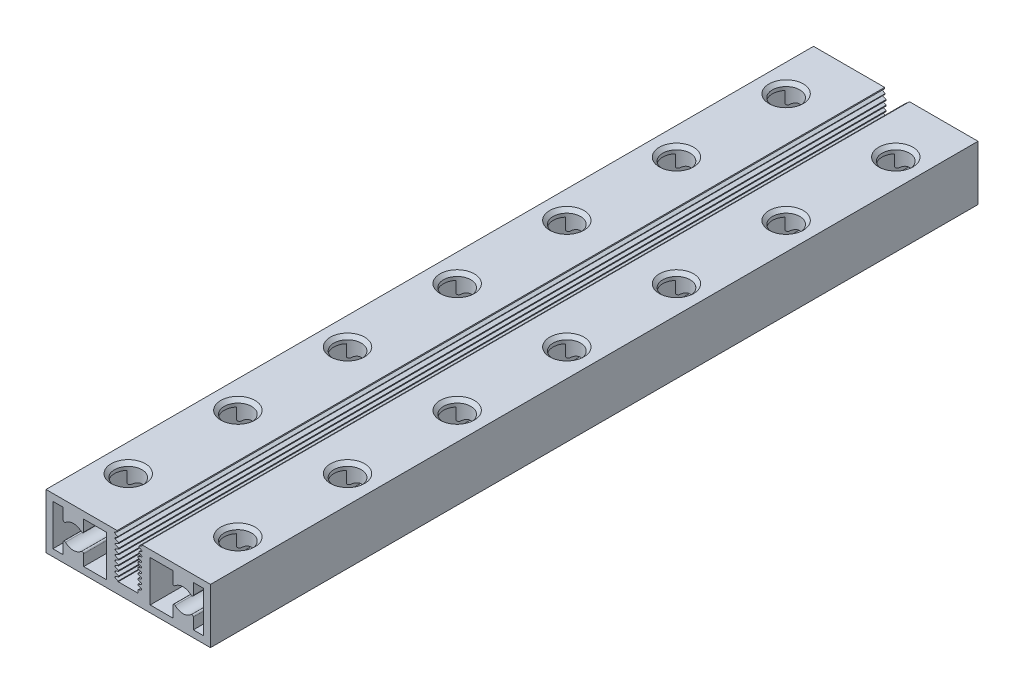
SolidWorks part; units mm, degrees
ref_plane "Front Plane" through (0, 0, 0) normal (0, 0, 1) x (1, 0, 0)
ref_plane "Top Plane" through (0, 0, 0) normal (0, 1, 0) x (1, 0, 0)
ref_plane "Right Plane" through (0, 0, 0) normal (1, 0, 0) x (0, 0, -1)
ref_plane "Plane1" through (0, 8, 0) normal (0, 1, 0) x (1, 0, 0)
sketch "Sketch1" plane through (0, 8, 0) normal (0, 1, 0) x (1, 0, 0)
  line L0 (-12, -112) -> (12, -112)
  line L1 (12, -112) -> (12, 0)
  line L2 (12, 0) -> (-12, 0)
  line L3 (-12, 0) -> (-12, -112)
extrude "Boss-Extrude1" add sketch "Sketch1" against normal blind 8
sketch "Sketch2" plane through (0, 0, 112) normal (0, 0, 1) x (1, 0, 0)
  line L0 (2, 8) -> (-1.62, 8)
  line L1 (-1.62, 8) -> (-1.62, 7.825)
  line L2 (-1.62, 7.825) -> (-2.0747, 7.5625)
  line L3 (-2.0747, 7.5625) -> (-1.4684, 7.2125)
  line L4 (-1.4684, 7.2125) -> (-2.0878, 6.8549)
  line L5 (-2.0878, 6.8549) -> (-1.2404, 6.5125)
  line L6 (-1.2404, 6.5125) -> (-2.1067, 6.1625)
  line L7 (-2.1067, 6.1625) -> (-1.2404, 5.8125)
  line L8 (-1.2404, 5.8125) -> (-2.1067, 5.4625)
  line L9 (-2.1067, 5.4625) -> (-1.2404, 5.1125)
  line L10 (-1.2404, 5.1125) -> (-2.1067, 4.7625)
  line L11 (-2.1067, 4.7625) -> (-1.2404, 4.4125)
  line L12 (-1.2404, 4.4125) -> (-2.1067, 4.0625)
  line L13 (-2.1067, 4.0625) -> (-1.2404, 3.7125)
  line L14 (-1.2404, 3.7125) -> (-2.1067, 3.3625)
  line L15 (-2.1067, 3.3625) -> (-1.2404, 3.0125)
  line L16 (-1.2404, 3.0125) -> (-2.1067, 2.6625)
  line L17 (-2.1067, 2.6625) -> (-1.2404, 2.3125)
  line L18 (-1.2404, 2.3125) -> (-2.1067, 1.9625)
  line L19 (-2.1067, 1.9625) -> (-1.46, 1.7012)
  line L20 (-1.46, 1.7012) -> (-1.46, 1.6)
  line L21 (-1.46, 1.6) -> (1.46, 1.6)
  line L22 (1.46, 1.6) -> (1.46, 2.0618)
  line L23 (1.46, 2.0618) -> (2.1067, 2.3231)
  line L24 (2.1067, 2.3231) -> (1.2404, 2.6731)
  line L25 (1.2404, 2.6731) -> (2.1067, 3.0231)
  line L26 (2.1067, 3.0231) -> (1.2404, 3.3731)
  line L27 (1.2404, 3.3731) -> (2.1067, 3.7231)
  line L28 (2.1067, 3.7231) -> (1.2404, 4.0731)
  line L29 (1.2404, 4.0731) -> (2.1067, 4.4231)
  line L30 (2.1067, 4.4231) -> (1.2404, 4.7731)
  line L31 (1.2404, 4.7731) -> (2.1067, 5.1231)
  line L32 (2.1067, 5.1231) -> (1.2404, 5.4731)
  line L33 (1.2404, 5.4731) -> (2.1067, 5.8231)
  line L34 (2.1067, 5.8231) -> (1.2404, 6.1731)
  line L35 (1.2404, 6.1731) -> (2.0878, 6.5155)
  line L36 (2.0878, 6.5155) -> (1.4684, 6.8731)
  line L37 (1.4684, 6.8731) -> (2.0747, 7.2231)
  line L38 (2.0747, 7.2231) -> (1.4684, 7.5731)
  line L39 (1.4684, 7.5731) -> (2, 7.88)
  line L40 (2, 7.88) -> (2, 8)
extrude "Cut-Extrude1" cut sketch "Sketch2" against normal through all
sketch "Sketch3" plane through (0, 0, 0) normal (0, 0, -1) x (-1, 0, 0)
  line L0 (-6.5, 2.6144) -> (-6.5, 1)
  line L1 (-6.5, 1) -> (-3.2, 1)
  line L2 (-3.2, 1) -> (-3.2, 7)
  line L3 (-3.2, 7) -> (-6.5, 7)
  line L4 (-6.5, 7) -> (-6.5, 5.3856)
  line L5 (-9.5, 5.3856) -> (-9.5, 7)
  line L6 (-9.5, 7) -> (-11, 7)
  line L7 (-11, 7) -> (-11, 1)
  line L8 (-11, 1) -> (-9.5, 1)
  line L9 (-9.5, 1) -> (-9.5, 2.6144)
  arc A0 (-6.5, 5.3856) -> (-6.8368, 5.2398) centre (-6.7, 5.3856) cw
  arc A1 (-6.8368, 5.2398) -> (-9.1632, 5.2398) centre (-8, 4) ccw
  arc A2 (-9.1632, 5.2398) -> (-9.5, 5.3856) centre (-9.3, 5.3856) cw
  arc A3 (-9.5, 2.6144) -> (-9.1632, 2.7602) centre (-9.3, 2.6144) cw
  arc A4 (-9.1632, 2.7602) -> (-6.8368, 2.7602) centre (-8, 4) ccw
  arc A5 (-6.8368, 2.7602) -> (-6.5, 2.6144) centre (-6.7, 2.6144) cw
extrude "Cut-Extrude2" cut sketch "Sketch3" against normal through all
sketch "Sketch4" plane through (0, 0, 112) normal (0, 0, 1) x (1, 0, 0)
  line L0 (-9.5, 7) -> (-11, 7)
  line L1 (-11, 7) -> (-11, 1)
  line L2 (-11, 1) -> (-9.5, 1)
  line L3 (-9.5, 1) -> (-9.5, 2.6144)
  line L4 (-6.5, 2.6144) -> (-6.5, 1)
  line L5 (-6.5, 1) -> (-3.2, 1)
  line L6 (-3.2, 1) -> (-3.2, 7)
  line L7 (-3.2, 7) -> (-6.5, 7)
  line L8 (-6.5, 7) -> (-6.5, 5.3856)
  line L9 (-9.5, 5.3856) -> (-9.5, 7)
  arc A0 (-9.5, 2.6144) -> (-9.1632, 2.7602) centre (-9.3, 2.6144) cw
  arc A1 (-9.1632, 2.7602) -> (-6.8368, 2.7602) centre (-8, 4) ccw
  arc A2 (-6.8368, 2.7602) -> (-6.5, 2.6144) centre (-6.7, 2.6144) cw
  arc A3 (-6.5, 5.3856) -> (-6.8368, 5.2398) centre (-6.7, 5.3856) cw
  arc A4 (-6.8368, 5.2398) -> (-9.1632, 5.2398) centre (-8, 4) ccw
  arc A5 (-9.1632, 5.2398) -> (-9.5, 5.3856) centre (-9.3, 5.3856) cw
extrude "Cut-Extrude3" cut sketch "Sketch4" against normal through all
hole_wizard "Ø4.0 (4) Diameter Hole1" positions "Sketch6" profile "Sketch5" hole size "Ø4.0" standard "ANSI Metric"
sketch "Sketch6" plane through (0, 8, 0) normal (0, 1, 0) x (1, 0, 0)
  point P0 (-8, -88)
  point P1 (-8, -104)
  point P2 (-8, -72)
  point P3 (-8, -56)
  point P4 (-8, -40)
  point P5 (-8, -24)
  point P6 (-8, -8)
  point P7 (8, -8)
  point P8 (8, -24)
  point P9 (8, -40)
  point P10 (8, -56)
  point P11 (8, -72)
  point P12 (8, -88)
  point P13 (8, -104)
sketch "Sketch5" plane through (-8, 8, 88) normal (1, 0, 0) x (0, 0, 1)
  line L0 (0, 0) -> (0, 10.8144)
  line L1 (0, 10.8144) -> (2, 10.8144)
  line L2 (2, 10.8144) -> (2, 0)
  line L5 (2, 0) -> (0, 0)
  line L10 (0, 10.8144) -> (-2, 10.8144) construction
  line L11 (0, -6.35) -> (0, 107.95) construction
  dimension "Hole Dia." = 4
  dimension "Hole Depth" = 10.8144
  dimension "Drill Angle" = 180
chamfer "Chamfer1" distance 0.169 angle 68 27 edges at (1.2404, 4.7731, 56) (-1.2404, 4.4125, 56) (-1.2404, 5.1125, 56) (2.1067, 5.1231, 56) (2.1067, 4.4231, 56) (-2.1067, 4.0625, 56) (-2.1067, 5.4625, 56) (1.2404, 5.4731, 56) (1.2404, 4.0731, 56) (-1.2404, 3.7125, 56) (-1.2404, 5.8125, 56) (2.1067, 5.8231, 56) (2.1067, 3.7231, 56) (-2.1067, 4.7625, 56) (-2.1067, 3.3625, 56) (-2.1067, 6.1625, 56) (1.2404, 6.1731, 56) (1.2404, 3.3731, 56) (-1.2404, 3.0125, 56) (-1.2404, 6.5125, 56) (2.1067, 3.0231, 56) (-2.1067, 2.6625, 56) (-2.0878, 6.8549, 56) (1.2404, 2.6731, 56) (-1.2404, 2.3125, 56) (2.1067, 2.3231, 56) (-2.1067, 1.9625, 56) first distance on face at (1.6736, 4.9481, 56) first distance on face at (-1.6736, 4.5875, 56) first distance on face at (-1.6736, 5.2875, 56) first distance on face at (1.6736, 5.2981, 56) first distance on face at (1.6736, 4.5981, 56) first distance on face at (-1.6736, 3.8875, 56) first distance on face at (1.6736, 5.6481, 56) first distance on face at (1.6736, 4.2481, 56) first distance on face at (-1.6736, 5.9875, 56) first distance on face at (1.6736, 5.9981, 56) first distance on face at (1.6736, 3.8981, 56) first distance on face at (-1.6736, 3.1875, 56) first distance on face at (1.6641, 6.3443, 56) first distance on face at (1.6736, 3.5481, 56) first distance on face at (-1.6641, 6.6837, 56) first distance on face at (1.6736, 3.1981, 56) first distance on face at (-1.6736, 2.4875, 56) first distance on face at (1.6736, 2.8481, 56) first distance on face at (1.6736, 2.4981, 56) first distance on face at (-1.7833, 1.8319, 56)
chamfer "Chamfer2" distance 0.5 angle 45 28 edges at (-8, 0, 10) (-8, 8, 106) (-8, 0, 74) (-8, 8, 42) (8, 8, 58) (-8, 0, 42) (-8, 0, 106) (-8, 8, 10) (-8, 8, 74) (8, 8, 26) (8, 8, 90) (-8, 0, 26) (-8, 0, 58) (-8, 0, 90) (-8, 8, 26) (-8, 8, 58) (-8, 8, 90) (8, 8, 10) (8, 8, 42) (8, 8, 74) (8, 8, 106) (8, 0, 10) (8, 0, 26) (8, 0, 42) (8, 0, 58) (8, 0, 74) (8, 0, 90) (8, 0, 106)
chamfer "Chamfer3" distance 0.0862 angle 60 6 edges at (-2.0747, 7.5625, 56) (1.4684, 7.5731, 56) (2.0878, 6.5155, 56) (1.4684, 6.8731, 56) (-1.4684, 7.2125, 56) (2.0747, 7.2231, 56) first distance on face at (-1.7716, 7.3875, 56) first distance on face at (1.7716, 7.3981, 56) first distance on face at (1.7781, 6.6943, 56) first distance on face at (-1.6998, 7.0789, 56)
